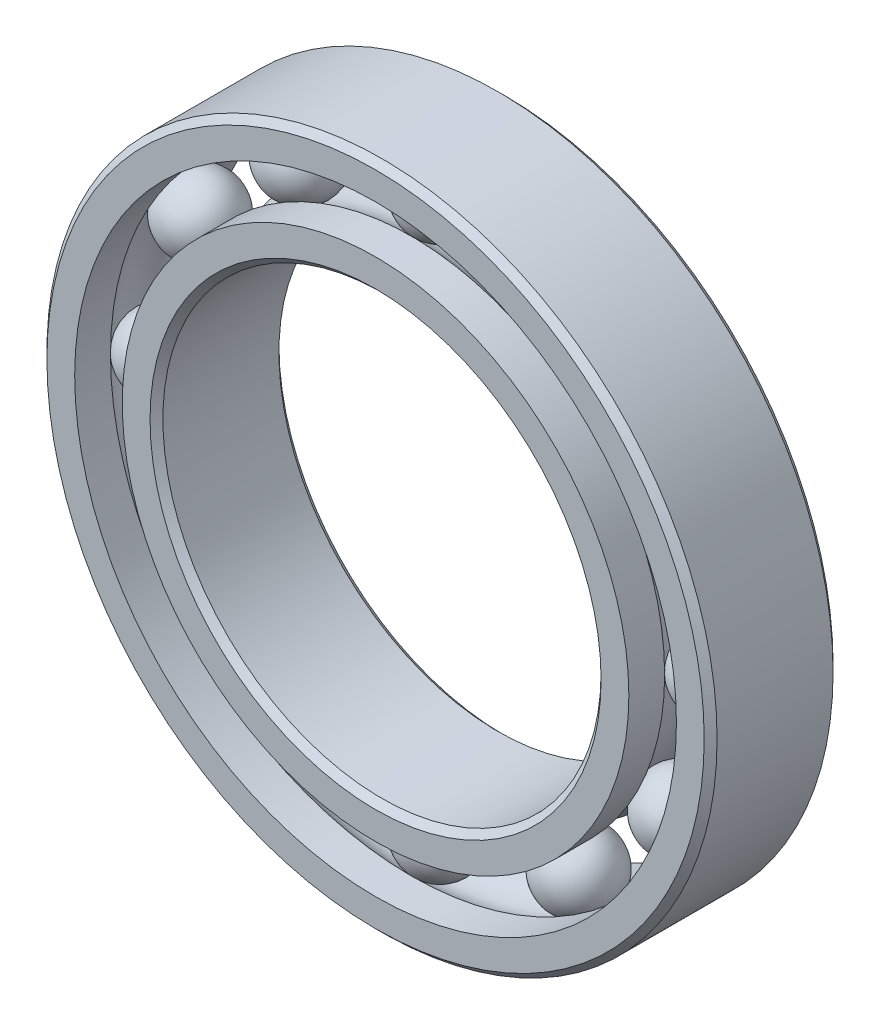
SolidWorks part; units mm, degrees
ref_plane "Front Plane" through (0, 0, 0) normal (0, 0, 1) x (1, 0, 0)
ref_plane "Top Plane" through (0, 0, 0) normal (0, 1, 0) x (1, 0, 0)
ref_plane "Right Plane" through (0, 0, 0) normal (1, 0, 0) x (0, 0, -1)
sketch "Sketch1" plane through (0, 0, 0) normal (1, 0, 0) x (0, 0, -1)
  line L0 (-2.5, 0) -> (2.5, 0) construction
  line L1 (0, 13) -> (0, -13) construction
  line L2 (2.25, 13) -> (-2.25, 13)
  line L3 (-2.25, 13) -> (-2.5, 12.75)
  line L4 (-2.5, 12.75) -> (-2.5, 11.6731)
  line L5 (-2.5, 11.6731) -> (-1.1111, 11.6731)
  line L6 (2.5, 11.6731) -> (1.1111, 11.6731)
  line L7 (2.5, 12.75) -> (2.5, 11.6731)
  line L8 (2.25, 13) -> (2.5, 12.75)
  line L9 (0, 13) -> (0, 10.75) construction
  line L10 (0, 10.75) -> (0, 8.5) construction
  arc A0 (-1.1111, 11.6731) -> (1.1111, 11.6731) centre (0, 10.75) cw
  point P14 (0, 8.5)
  dimension "Width" = 5
  dimension "OD" = 26
  dimension "D1" = 45
  dimension "D2" = 0.25
  dimension "Shaft Dia" = 17
  dimension "D3" = 2.2222
  dimension "D4" = 0.9231
revolve "Revolve1" add sketch "Sketch1" angle 360 about L0
sketch "Sketch3" plane through (0, 0, 0) normal (1, 0, 0) x (0, 0, -1)
  line L0 (-2.5, 9.8269) -> (-1.1111, 9.8269)
  line L1 (0, 13) -> (0, -13) construction
  line L2 (-2.5, 12.75) -> (-2.5, 11.6731) construction
  line L3 (-2.5, 9.8269) -> (-2.5, 8.75)
  line L4 (-2.25, 13) -> (-2.5, 12.75) construction
  line L5 (-2.5, 8.75) -> (-2.25, 8.5)
  line L6 (-2.25, 8.5) -> (2.25, 8.5)
  line L7 (2.25, 13) -> (2.25, -13) construction
  line L8 (2.25, 8.5) -> (2.5, 8.75)
  line L9 (2.5, -12.75) -> (2.5, 12.75) construction
  line L10 (2.5, 8.75) -> (2.5, 9.8269)
  line L11 (2.5, 9.8269) -> (1.1111, 9.8269)
  line L13 (2.25, 13) -> (2.5, 12.75) construction
  arc A0 (1.1111, 11.6731) -> (-1.1111, 11.6731) centre (0, 10.75) ccw construction
  arc A1 (1.1111, 9.8269) -> (-1.1111, 9.8269) centre (0, 10.75) cw
revolve "Revolve3" add sketch "Sketch3" angle 360 about L0
sketch "Sketch4" plane through (0, 0, 0) normal (1, 0, 0) x (0, 0, -1)
  line L0 (-1.4445, 10.75) -> (1.4445, 10.75)
  arc A2 (-1.4445, 10.75) -> (1.4445, 10.75) centre (0, 10.75) cw
  arc A3 (1.1111, 11.6731) -> (-1.1111, 11.6731) centre (0, 10.75) ccw construction
revolve "Revolve4" add sketch "Sketch4" angle 360 about L0
ref_axis "Axis1" through (0, 0, -2.5) along (0, 0, 1)
pattern_circular "CirPattern1" count 12 every 30 about axis through (0, 0, -2.5) along (0, 0, 1) of bodies 104
sketch "Sketch5" plane through (0, 0, 0) normal (1, 0, 0) x (0, 0, -1)
  line L0 (-2.5, 11.6731) -> (-1.1111, 11.6731) construction
  line L1 (-2.375, 11.6731) -> (-1.4445, 11.6731)
  line L2 (-2.375, 11.6731) -> (-2.375, 9.8269)
  line L3 (-2.375, 9.8269) -> (-1.4445, 9.8269)
  line L4 (-1.4445, 11.6731) -> (-1.4445, 9.8269)
  line L5 (-2.5, 9.8269) -> (-1.1111, 9.8269) construction
  line L6 (2.5, 11.6731) -> (1.1111, 11.6731) construction
  line L7 (2.375, 11.6731) -> (1.4445, 11.6731)
  line L8 (2.375, 11.6731) -> (2.375, 9.8269)
  line L9 (2.375, 9.8269) -> (1.4445, 9.8269)
  line L10 (1.4445, 11.6731) -> (1.4445, 9.8269)
  line L11 (2.5, 9.8269) -> (1.1111, 9.8269) construction
  line L12 (-2.25, 13) -> (-2.5, 12.75) construction
  point P18 (-2.375, 12.875)
revolve "Revolve5" [suppressed] add sketch "Sketch5" angle 360 about L0
equation "\"D2@Sketch1\" = \"Width@Sketch1\"*.05"
equation "\"D3@Sketch1\" = \"Width@Sketch1\"/2.25"
equation "\"D4@Sketch1\" = (((\"OD@Sketch1\"-\"Width@Sketch1\")/2)/3.25)/3.5"
equation "\"D2@CirPattern1\" = 360/\"Balls@CirPattern1\""
